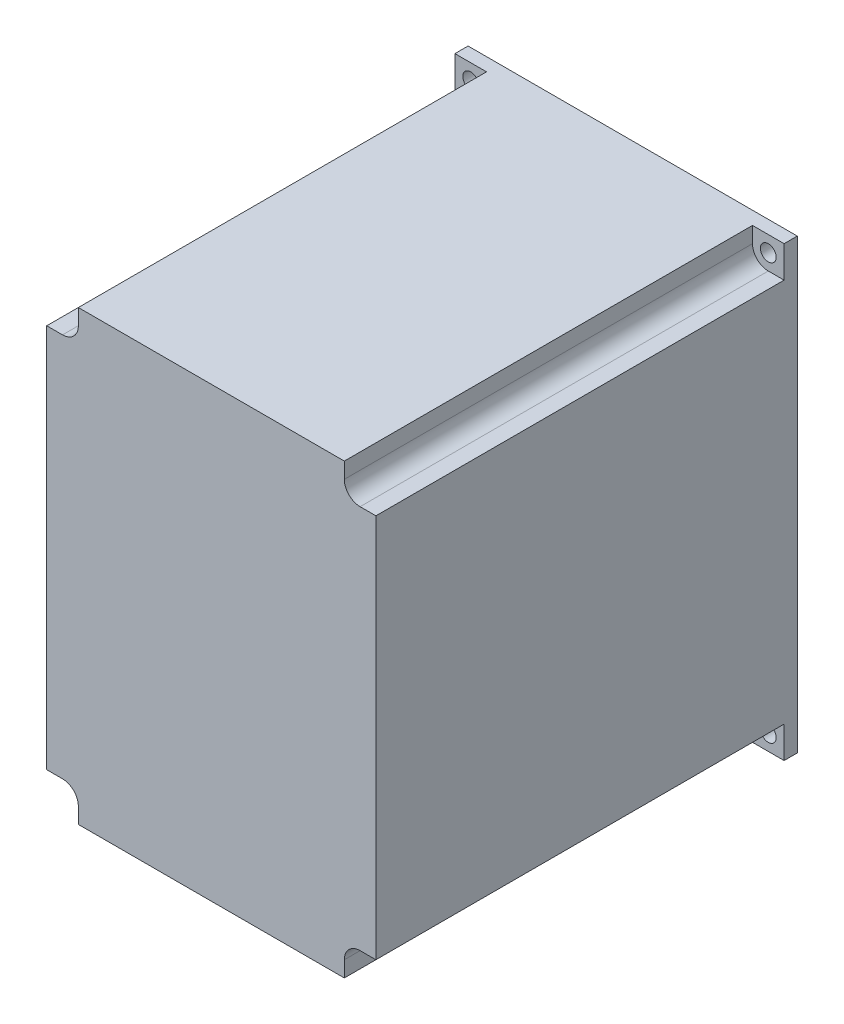
SolidWorks part; units mm, degrees
material "Nylon 6/10"
ref_plane "Front Plane" through (0, 0, 0) normal (0, 0, 1) x (1, 0, 0)
ref_plane "Top Plane" through (0, 0, 0) normal (0, 1, 0) x (1, 0, 0)
ref_plane "Right Plane" through (0, 0, 0) normal (1, 0, 0) x (0, 0, -1)
sketch "Sketch1" plane through (0, 0, 0) normal (0, 0, 1) x (1, 0, 0)
  line L1 (-62.5, 85) -> (62.5, 85)
  line L2 (-62.5, 85) -> (-62.5, -85)
  line L3 (-62.5, -85) -> (62.5, -85)
  line L4 (62.5, 85) -> (62.5, -85)
  line L5 (-62.5, 85) -> (62.5, -85) construction
  line L6 (-62.5, -85) -> (62.5, 85) construction
  point P0 (0, 0)
  dimension "D1" = 125
  dimension "D2" = 170
extrude "Boss-Extrude1" add sketch "Sketch1" along normal blind 160
sketch "Sketch2" plane through (0, 0, 160) normal (0, 0, 1) x (1, 0, 0)
  line L0 (-62.5, 85) -> (-50.5, 85)
  line L1 (62.5, 85) -> (-62.5, 85) construction
  line L2 (-50.5, 85) -> (-50.5, 79)
  line L3 (-56.5, 73) -> (-62.5, 73)
  line L4 (-62.5, 85) -> (-62.5, -85) construction
  line L5 (-62.5, 73) -> (-62.5, 85)
  arc A0 (-50.5, 79) -> (-56.5, 73) centre (-56.5, 79) cw
  circle A1 centre (-56.5, 79) radius 3
  line M8 (62.5, 85) -> (-62.5, 85)
  line M9 (-62.5, 85) -> (-62.5, -85)
  dimension "D1" = 6
  dimension "D3" = 6
  dimension "D2" = 6
extrude "Cut-Extrude1" cut sketch "Sketch2" against normal offset from surface (155 mm away) 5 contours A1 | A0 L2 L3 A1 M8 M9 region at (-56.5, 84.8303, 160) region at (-56.5, 79, 160) up to face at (0, 0, 0)
extrude "Cut-Extrude2" cut sketch "Sketch2<3>" against normal through all contours A1 region at (-56.5, 79, 160)
sketch "Sketch2<3>" plane through (0, 0, 160) normal (0, 0, 1) x (1, 0, 0) same geometry as "Sketch2"
mirror "Mirror1" about plane through (0, 0, 0) normal (0, 1, 0) of "Cut-Extrude2", "Cut-Extrude1"
mirror "Mirror2" about plane through (0, 0, 0) normal (1, 0, 0) of "Mirror1"
